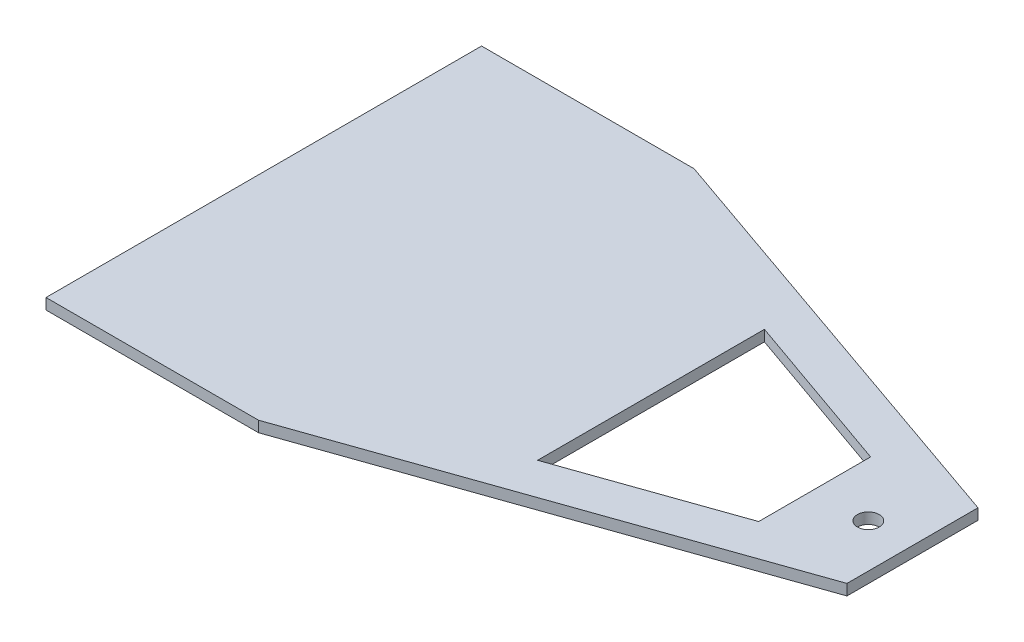
SolidWorks part; units mm, degrees
ref_plane "Front Plane" through (0, 0, 0) normal (0, 0, 1) x (1, 0, 0)
ref_plane "Top Plane" through (0, 0, 0) normal (0, 1, 0) x (1, 0, 0)
ref_plane "Right Plane" through (0, 0, 0) normal (1, 0, 0) x (0, 0, -1)
sketch "Sketch1" plane through (0, 0, 0) normal (0, 1, 0) x (1, 0, 0)
  line L1 (0, 0) -> (61.976, 0)
  line L2 (0, 0) -> (0, 127)
  line L3 (0, 127) -> (61.976, 127)
  line L9 (188.976, 44.5717) -> (188.976, 82.7785)
  line L16 (188.976, 82.7785) -> (61.976, 127)
  line L17 (61.976, 0) -> (188.976, 44.5717)
  line L20 (173.101, 63.5) -> (160.4782, 63.5)
  line L21 (160.4782, 63.5) -> (160.4782, 79.9618)
  line L22 (160.4782, 63.5) -> (160.4782, 47.3262)
  line L24 (112.776, 63.5) -> (112.776, 30.5567)
  line L25 (112.776, 30.5567) -> (112.776, 96.7044)
  line L28 (112.776, 30.5567) -> (160.4782, 47.3262)
  line L30 (160.4782, 79.9618) -> (112.776, 96.7044)
  circle A0 centre (176.276, 63.5) radius 3.175
  dimension "D6" = 6.35
  dimension "D8" = 63.5
  dimension "D1" = 127
  dimension "D2" = 61.976
  dimension "D3" = 38.2069
  dimension "D4" = 134.4788
  dimension "D5" = 134.5943
  dimension "D7" = 176.276
  dimension "D9" = 109.339
extrude "Boss-Extrude1" add sketch "Sketch1" along normal blind 3.175 contours L1 L17 L9 L16 L3 L2 A0 L22 L28 L24 L25 L30 L21 region at (70.099, 0, -63.5271)
